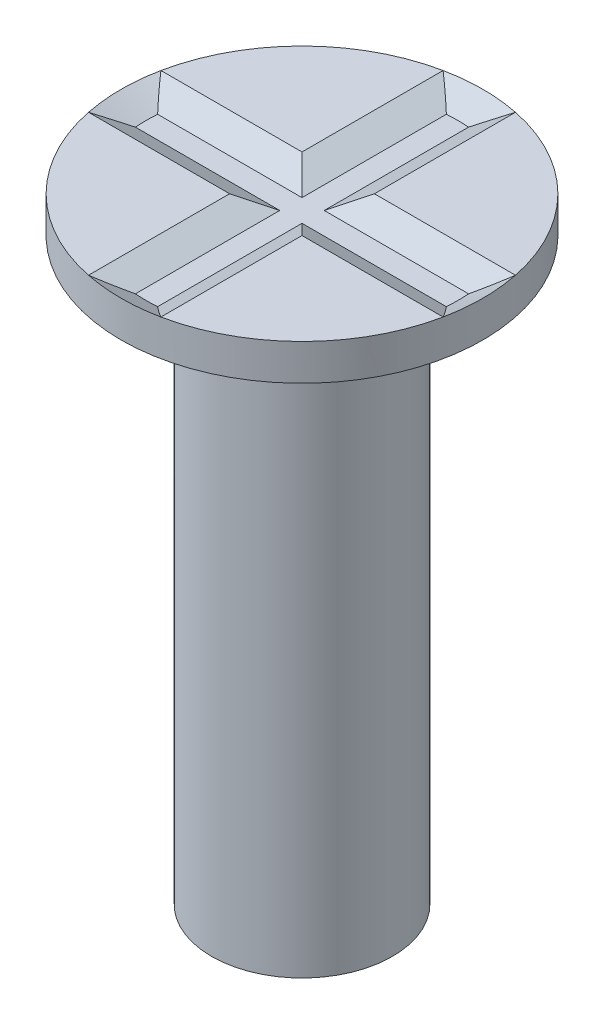
SolidWorks part; units mm, degrees
ref_plane "Front" through (0, 0, 0) normal (0, 0, 1) x (1, 0, 0)
ref_plane "Top" through (0, 0, 0) normal (0, 1, 0) x (1, 0, 0)
ref_plane "Right" through (0, 0, 0) normal (1, 0, 0) x (0, 0, -1)
sketch "Sketch1" plane through (0, 0, 0) normal (0, 1, 0) x (1, 0, 0)
  circle A0 centre (0, 0) radius 0.5
  circle A1 centre (0, 0) radius 0.25
  dimension "D1" = 1
  dimension "D2" = 0.5
extrude "Boss-Extrude1" add sketch "Sketch1" against normal blind 0.1 contours A0
extrude "Boss-Extrude2" add sketch "Sketch1<3>" against normal blind 1.6 from surface contours A1 region at (0, 0, 0) starting at face at (0, -0.1, 0.5)
sketch "Sketch1<3>" plane through (0, 0, 0) normal (0, 1, 0) x (1, 0, 0) same geometry as "Sketch1"
sketch "Sketch2" plane through (0, 0, 0) normal (0, 1, 0) x (1, 0, 0)
  line L0 (-0.1, 0.5229) -> (-0.1, -0.5733)
  line L1 (-0.1, -0.5733) -> (0.1, -0.5733)
  line L2 (0.1, -0.5733) -> (0.1, 0.5229)
  line L3 (0.1, 0.5229) -> (-0.1, 0.5229)
  line L4 (-0.6158, 0.1) -> (0.6078, 0.1)
  line L5 (0.6078, 0.1) -> (0.6078, -0.1)
  line L6 (0.6078, -0.1) -> (-0.6158, -0.1)
  line L7 (-0.6158, -0.1) -> (-0.6158, 0.1)
  circle M5 centre (0, 0) radius 0.5
  dimension "D1" = 0.2
  dimension "D2" = 0.1
  dimension "D3" = 0.1
extrude "Cut-Extrude1" cut sketch "Sketch2" against normal blind 0.04 draft 60 contours L6 L0 L4 M5 | L0 L4 L2 M5 | L6 L4 L2 M5 | L2 L6 L0 M5 | L6 L2 L4 L0 region at (0, 0, -0.2983) region at (0, 0, 0) region at (-0.2983, 0, 0) region at (0, 0, 0.2983) region at (0.2983, 0, 0)
